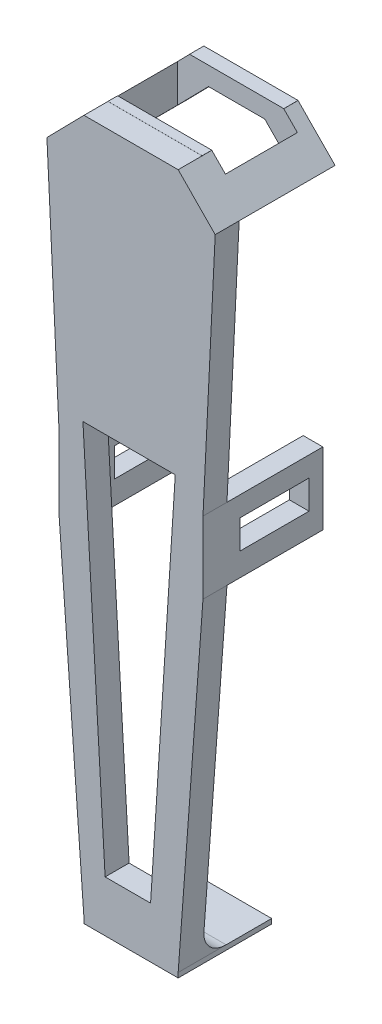
SolidWorks part; units mm, degrees
material "PLA"
ref_plane "Front Plane" through (0, 0, 0) normal (0, 0, 1) x (1, 0, 0)
ref_plane "Top Plane" through (0, 0, 0) normal (0, 1, 0) x (1, 0, 0)
ref_plane "Right Plane" through (0, 0, 0) normal (1, 0, 0) x (0, 0, -1)
sketch "Sketch1" plane through (0, 0, 0) normal (0, 0, 1) x (1, 0, 0)
  line L0 (-37.3414, 34.6091) -> (22.6586, 34.6091)
  line L1 (22.6586, 34.6091) -> (50.9429, 6.3248)
  line L2 (50.9429, 6.3248) -> (50.9429, -53.6752)
  line L3 (50.9429, -53.6752) -> (22.6586, -81.9594)
  line L4 (22.6586, -81.9594) -> (-37.3414, -81.9594)
  line L5 (-37.3414, -81.9594) -> (-64.6578, -54.643)
  line L6 (-64.6578, -54.643) -> (-64.6578, 5.357)
  line L7 (-64.6578, 5.357) -> (-37.3414, 34.6091)
  line L8 (-27.6371, 26.0388) -> (-43.235, 10.1409)
  line L13 (-8.1397, -94.0869) -> (21.8603, -94.0869)
  line L15 (-27.6371, 26.0388) -> (-19.7574, 18.3077)
  line L16 (-43.235, 10.1409) -> (-35.3553, 2.4098)
  line L17 (-19.7574, 18.3077) -> (-35.3553, 2.4098)
  line L18 (-8.1397, 25.9131) -> (-8.1397, 18.1821)
  line L19 (-27.7871, 25.9131) -> (11.5077, 25.9131)
  line L20 (-27.7871, 25.9131) -> (-27.7871, 18.1821)
  line L21 (-27.7871, 18.1821) -> (11.5077, 18.1821)
  line L22 (11.5077, 25.9131) -> (11.5077, 18.1821)
  line L23 (-8.1397, 18.1821) -> (-8.1397, 25.9131) construction
  line L24 (-27.7871, 22.0476) -> (11.5077, 22.0476) construction
  line L25 (26.9557, 10.1409) -> (19.0759, 2.4098)
  line L26 (3.478, 18.3077) -> (19.0759, 2.4098)
  line L27 (11.3577, 26.0388) -> (3.478, 18.3077)
  line L28 (11.3577, 26.0388) -> (26.9557, 10.1409)
  line L29 (21.8603, -94.0869) -> (-38.1397, -94.0869)
  line L30 (21.8603, -94.0869) -> (21.8603, -124.0869)
  line L31 (21.8603, -124.0869) -> (-38.1397, -124.0869)
  line L32 (-38.1397, -94.0869) -> (-38.1397, -124.0869)
  line L33 (-30.3382, -94.0869) -> (13.6618, -94.0869)
  line L34 (-30.3382, -94.0869) -> (-30.3382, -124.0869)
  line L35 (-30.3382, -124.0869) -> (13.6618, -124.0869)
  line L36 (13.6618, -94.0869) -> (13.6618, -124.0869)
  line L37 (-8.3382, -124.0869) -> (-8.3382, -94.0869) construction
  line L38 (-30.3382, -109.0869) -> (13.6618, -109.0869) construction
  point P12 (-8.1397, 22.0476)
  point P17 (-8.3382, -109.0869)
  dimension "D1" = 135
  dimension "D2" = 135
  dimension "D3" = 40
  dimension "D4" = 135
  dimension "D5" = 120
  dimension "D6" = 30
  dimension "D7" = 22.2719
  dimension "D8" = 11.039
  dimension "D9" = 7.7311
  dimension "D10" = 39.2948
  dimension "D11" = 60
  dimension "D12" = 30
  dimension "D13" = 44
extrude "Boss-Extrude1" add sketch "Sketch1" along normal blind 40 contours L21 L20 L8 L16 L17 | L32 L29 L31 | L28 L22 L21 L26 L25 | L29 L36 L31 L30 | L21 L22 L19 L20 region at (-32.4791, 13.2115, 0) region at (16.1997, 13.2115, 0) region at (17.7611, -109.0869, 0) region at (-34.2389, -109.0869, 0)
sketch "Sketch2" plane through (0, 0, 40) normal (0, 0, 1) x (1, 0, 0)
  line L0 (-43.235, 10.1409) -> (-38.1397, -94.0869)
  line L1 (26.9557, 10.1409) -> (21.8603, -94.0869)
  line L2 (-43.235, 10.1409) -> (-27.7871, 25.8859)
  line L3 (-27.7871, 25.8859) -> (11.5077, 25.8859)
  line L4 (11.5077, 25.8859) -> (26.9557, 10.1409)
  line L5 (-27.7871, -264.1141) -> (11.5077, -264.1141)
  line L6 (-38.1397, -94.0869) -> (-38.1397, -124.0869)
  line L7 (-38.1397, -124.0869) -> (-27.7871, -264.1141)
  line L8 (21.8603, -94.0869) -> (21.8603, -124.0869)
  line L9 (21.8603, -124.0869) -> (11.5077, -264.1141)
extrude "Boss-Extrude2" add sketch "Sketch2" along normal blind 10
sketch "Sketch3" plane through (0, -264.1141, 0) normal (0, -1, 0) x (1, 0, 0)
  line L1 (11.5077, 50) -> (-27.7823, 50)
  line L2 (11.5077, 50) -> (11.5077, 11)
  line L3 (11.5077, 11) -> (-27.7823, 11)
  line L4 (-27.7823, 50) -> (-27.7823, 11)
  dimension "D1" = 39
  dimension "D2" = 39.29
extrude "Boss-Extrude3" add sketch "Sketch3" along normal blind 2
fillet "Fillet1" radius 10 1 edges at (-8.1373, -264.1141, 40)
sketch "Sketch4" plane through (-38.1397, 0, 0) normal (-1, 0, 0) x (0, 0, 1)
  line L1 (5.7663, -102.4295) -> (34.6083, -102.4295)
  line L2 (5.7663, -102.4295) -> (5.7663, -114.4295)
  line L3 (5.7663, -114.4295) -> (34.6083, -114.4295)
  line L4 (34.6083, -102.4295) -> (34.6083, -114.4295)
  dimension "D1" = 12
  dimension "D2" = 28.842
extrude "Cut-Extrude1" cut sketch "Sketch4" against normal blind 200
sketch "Sketch5" plane through (0, 25.9131, 0) normal (0, 1, 0) x (1, 0, 0)
  line L1 (-32.8131, -5.9548) -> (17.1869, -5.9548)
  line L2 (-32.8131, -5.9548) -> (-32.8131, -35.9635)
  line L3 (-32.8131, -35.9635) -> (17.1869, -35.9635)
  line L4 (17.1869, -5.9548) -> (17.1869, -35.9635)
  dimension "D1" = 30.0088
  dimension "D2" = 50
extrude "Cut-Extrude2" cut sketch "Sketch5" against normal blind 50
sketch "Sketch6" plane through (0, 0, 50) normal (0, 0, 1) x (1, 0, 0)
  line L0 (-18.9621, -244.829) -> (0, -244.829)
  line L1 (0, -244.829) -> (10.2966, -84.9429)
  line L2 (10.2966, -84.9429) -> (-28.2206, -84.9429)
  line L3 (-28.2206, -84.9429) -> (-18.9621, -244.829)
extrude "Cut-Extrude3" cut sketch "Sketch6" against normal blind 30
